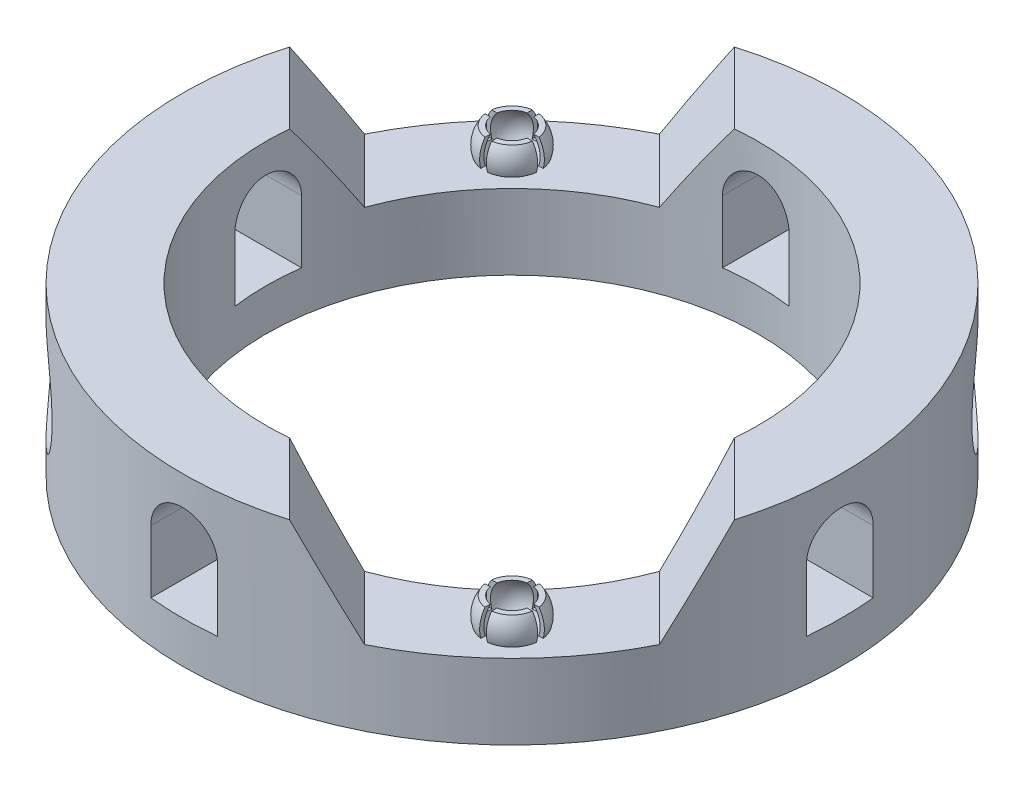
SolidWorks part; units mm, degrees
ref_plane "Front Plane" through (0, 0, 0) normal (0, 0, 1) x (1, 0, 0)
ref_plane "Top Plane" through (0, 0, 0) normal (0, 1, 0) x (1, 0, 0)
ref_plane "Right Plane" through (0, 0, 0) normal (1, 0, 0) x (0, 0, -1)
sketch "Sketch1" plane through (0, 0, 0) normal (0, 1, 0) x (1, 0, 0)
  circle A0 centre (0, 0) radius 29.5
  circle A1 centre (0, 0) radius 39.5
  dimension "D1" = 59
  dimension "D2" = 79
extrude "Boss-Extrude1" add sketch "Sketch1" along normal blind 20
ref_plane "Plane1" through (0, 0, 0) normal (0.7071, 0, -0.7071) x (-0.7071, 0, -0.7071)
sketch "Sketch2" plane through (0, 0, 0) normal (1, 0, 0) x (0, 0, -1)
  line L0 (0, 0) -> (0, 30.0667) construction
  line L1 (4, 5) -> (-4, 5)
  line L2 (-4, 5) -> (-4, 12.5)
  line L3 (4, 5) -> (4, 12.5)
  arc A0 (-4, 12.5) -> (4, 12.5) centre (0, 12.5) cw
  dimension "D6" = 4
  dimension "D1" = 8
  dimension "D2" = 4
  dimension "D3" = 5
  dimension "D4" = 7.5
  dimension "D5" = 7.5
extrude "Cut-Extrude1" cut sketch "Sketch2" against normal through all
extrude "Cut-Extrude2" cut sketch "Sketch2<2>" along normal through all
sketch "Sketch2<2>" plane through (0, 0, 0) normal (1, 0, 0) x (0, 0, -1) same geometry as "Sketch2"
mirror "Mirror1" about plane through (0, 0, 0) normal (0.7071, 0, -0.7071) of "Cut-Extrude2", "Cut-Extrude1"
sketch "Sketch4" plane through (0, 0, 0) normal (0.7071, 0, -0.7071) x (-0.7071, 0, -0.7071)
  line L0 (0, 0) -> (0, 44.1067) construction
  circle A0 centre (0, 10) radius 3.175
  dimension "D1" = 6.35
  dimension "D2" = 10
extrude "Cut-Extrude3" cut sketch "Sketch4" against normal up to next
extrude "Cut-Extrude4" cut sketch "Sketch4<2>" along normal up to next
sketch "Sketch4<2>" plane through (0, 0, 0) normal (0.7071, 0, -0.7071) x (-0.7071, 0, -0.7071) same geometry as "Sketch4"
ref_plane "Plane2" through (0, 0, 0) normal (0.7071, 0, 0.7071) x (0.7071, 0, -0.7071)
sketch "Sketch5" plane through (0, 20, 0) normal (0, 1, 0) x (1, 0, 0)
  line L0 (13.6827, -13.6827) -> (-13.6827, 13.6827) construction
  line L1 (-27.9307, 27.9307) -> (27.9307, -27.9307) construction
  line L2 (25.4558, -28.9914) -> (28.9914, -25.4558)
  line L3 (25.4558, -28.9914) -> (19.799, -23.3345)
  line L4 (28.9914, -25.4558) -> (23.3345, -19.799)
  line L5 (19.799, -23.3345) -> (23.3345, -19.799)
  line L6 (25.4558, -28.9914) -> (23.3345, -19.799) construction
  line L7 (28.9914, -25.4558) -> (19.799, -23.3345) construction
  circle A0 centre (0, 0) radius 39.5 construction
  circle A1 centre (0, 0) radius 29.5 construction
  point P7 (24.3952, -24.3952)
  dimension "D1" = 34.5
  dimension "D2" = 8
  dimension "D3" = 5
extrude "Boss-Extrude2" add sketch "Sketch5" along normal blind 13
sketch "Sketch6" plane through (1.7678, 0, -1.7678) normal (0.7071, 0, -0.7071) x (-0.7071, 0, -0.7071)
  line L0 (-38.5, 33) -> (-38.5, 20) construction
  line L1 (-38.5, 33) -> (-30.5, 33) construction
  line L2 (-30.5, 33) -> (-30.5, 20) construction
  line L4 (-38.5, 28) -> (-38.5, 33)
  line L8 (-38.5, 33) -> (-30.5, 33)
  line L9 (-30.5, 33) -> (-30.5, 28)
  arc A0 (-38.5, 28) -> (-30.5, 28) centre (-34.5, 28) cw
  dimension "D3" = 4
  dimension "D1" = 4
  dimension "D2" = 5
extrude "Cut-Extrude7" cut sketch "Sketch6" against normal up to next
sketch "Sketch7" plane through (1.7678, 0, -1.7678) normal (0.7071, 0, -0.7071) x (-0.7071, 0, -0.7071)
  circle A0 centre (-34.5, 28) radius 1
  dimension "D1" = 2
extrude "Cut-Extrude8" cut sketch "Sketch7" against normal up to next
ref_plane "Plane3" through (27.9307, 0, -27.9307) normal (0.7071, 0, -0.7071) x (-0.7071, 0, -0.7071)
sketch "Sketch8" plane through (27.9307, 0, -27.9307) normal (0.7071, 0, -0.7071) x (-0.7071, 0, -0.7071)
  circle A0 centre (0, 10) radius 6.35
  dimension "D1" = 12.7
extrude "Cut-Extrude9" cut sketch "Sketch8" against normal blind 1
mirror "Mirror3" about plane through (0, 0, 0) normal (0.7071, 0, -0.7071) of "Cut-Extrude9"
ref_plane "Plane4" through (0, 0, 0) normal (0.7071, 0, -0.7071) x (-0.7071, 0, -0.7071)
ref_plane "Plane5" through (0, 10, 0) normal (0, 1, 0) x (1, 0, 0)
ref_axis "Ball Join Axis" through (-41.2502, 10, -41.2502) along (0.7071, 0, 0.7071)
sketch "Sketch9" plane through (0, 20, 0) normal (0, 1, 0) x (1, 0, 0)
  line L3 (-17.6234, 26.1087) -> (-21.9323, 30.4175)
  line L4 (-26.1087, 17.6234) -> (-30.4175, 21.9323)
  line L5 (-41.2502, 41.2502) -> (45.8258, -45.8258) construction
  arc A0 (-17.6234, 26.1087) -> (-26.1087, 17.6234) centre (0, 0) ccw
  arc A1 (-21.9323, 30.4175) -> (-30.4175, 21.9323) centre (0, 0) ccw
  dimension "D3" = 37.5
  dimension "D4" = 31.5
  dimension "D1" = 6
  dimension "D2" = 6
extrude "Cut-Extrude11" cut sketch "Sketch9" against normal blind 15 contours A1 L4 A0 L3
sketch "Sketch10" plane through (0, 0, 0) normal (0.7071, 0, 0.7071) x (0.7071, 0, -0.7071)
  circle A0 centre (0, 10) radius 1.5
  dimension "D2" = 3
  dimension "D1" = 0
extrude "Cut-Extrude12" cut sketch "Sketch10" against normal blind 40
ref_plane "Plane8" through (0, 35, 0) normal (0, 1, 0) x (1, 0, 0)
sketch "Sketch15" plane through (0, 35, 0) normal (0, 1, 0) x (1, 0, 0)
  line L0 (-17.6564, 35.3341) -> (-10.0556, 27.7333)
  line L1 (-35.3341, 17.6564) -> (-27.7333, 10.0556)
  line L2 (10.0556, -27.7333) -> (17.6564, -35.3341)
  line L3 (27.7333, -10.0556) -> (35.3341, -17.6564)
  line L4 (-41.2502, 41.2502) -> (45.8258, -45.8258) construction
  arc A0 (17.6564, -35.3341) -> (35.3341, -17.6564) centre (0, 0) ccw
  arc A1 (-10.0556, 27.7333) -> (-27.7333, 10.0556) centre (0, 0) ccw
  arc A2 (-17.6564, 35.3341) -> (-35.3341, 17.6564) centre (0, 0) ccw
  arc A3 (10.0556, -27.7333) -> (27.7333, -10.0556) centre (0, 0) ccw
  dimension "D2" = 79
  dimension "D3" = 12.5
  dimension "D5" = 29.5
  dimension "D1" = 12.5
  dimension "D4" = 0
  dimension "0" = 0
extrude "Boss-Extrude3" add sketch "Sketch15" against normal through all contours A3 L2 A0 L3 | A1 L1 A2 L0 region at (23.8265, 35, 23.8265)
ref_plane "Plane9" through (0, 9, 0) normal (0, -1, 0) x (-1, 0, 0)
extrude "Cut-Extrude14" cut sketch "Sketch15<5>" against normal up to surface (26 mm away) contours A3 L2 A0 L3 | A2 L1 A1 L0 region at (23.8265, 35, 23.8265) up to plane "Plane9"
sketch "Sketch15<5>" plane through (0, 35, 0) normal (0, 1, 0) x (1, 0, 0) same geometry as "Sketch15"
ref_plane "Plane10" through (0, 10, 0) normal (0, 1, 0) x (1, 0, 0)
sketch "Sketch17" plane through (0, 10, 0) normal (0, 1, 0) x (1, 0, 0)
  line L5 (-41.2502, 41.2502) -> (45.8258, -45.8258) construction
  point P0 (-24.3952, 24.3952)
  point P1 (24.3952, -24.3952)
  dimension "D1" = 34.5
  dimension "D2" = 0
  dimension "D3" = 0
  dimension "D4" = 34.5
sketch "Sketch18" plane through (0, 10, 0) normal (0, 1, 0) x (1, 0, 0)
  line L0 (-24.3952, 27.8952) -> (-24.3952, 20.8952)
  line L1 (24.3952, -20.8952) -> (24.3952, -27.8952)
  arc A0 (-24.3952, 20.8952) -> (-24.3952, 27.8952) centre (-24.3952, 24.3952) ccw
  arc A1 (24.3952, -27.8952) -> (24.3952, -20.8952) centre (24.3952, -24.3952) ccw
revolve "Cut-Revolve1" cut sketch "Sketch18" angle 360 about L0 region at (-22.9097, 10, -24.3952)
revolve "Cut-Revolve2" cut sketch "Sketch18<3>" angle 360 about L1 region at (25.8806, 10, 24.3952)
sketch "Sketch18<3>" plane through (0, 10, 0) normal (0, 1, 0) x (1, 0, 0) same geometry as "Sketch18"
chamfer "Chamfer2" distance 11 angle 30 2 edges at (-31.5337, 20, -13.856) (13.856, 20, 31.5337) first distance on face at (-31.5337, 14.5, -13.856) first distance on face at (13.856, 14.5, 31.5337)
chamfer "Chamfer3" distance 11 angle 30 2 edges at (31.5337, 20, 13.856) (-13.856, 20, -31.5337) first distance on face at (31.5337, 14.5, 13.856) first distance on face at (-13.856, 14.5, -31.5337)
sketch "Sketch21" plane through (0, 0, 0) normal (0.7071, 0, -0.7071) x (-0.7071, 0, -0.7071)
  line L0 (-34.5, 13.5) -> (-34.5, 13)
  line L1 (-34.5, 7) -> (-34.5, 6.5)
  arc A0 (-34.5, 6.5) -> (-34.5, 13.5) centre (-34.5, 10) ccw
  arc A1 (-34.5, 7) -> (-34.5, 13) centre (-34.5, 10) ccw
  dimension "D1" = 3.5
revolve "Revolve1" add sketch "Sketch21" angle 360 about L0
ref_plane "Plane11" through (0, 12, 0) normal (0, 1, 0) x (1, 0, 0)
sketch "Sketch24" plane through (0, 12, 0) normal (0, 1, 0) x (1, 0, 0)
  circle A0 centre (24.3952, -24.3952) radius 3.5
  dimension "D1" = 0
extrude "Cut-Extrude15" cut sketch "Sketch24" along normal through all
sketch "Sketch26" plane through (0, 12, 0) normal (0, 1, 0) x (1, 0, 0)
  line L0 (23.9952, -24.7952) -> (23.9952, -27.8952)
  line L1 (20.9181, -23.9952) -> (23.9952, -23.9952)
  line L3 (20.9181, -24.7952) -> (23.9952, -24.7952)
  line L6 (23.9952, -20.9181) -> (23.9952, -23.9952)
  line L7 (23.9952, -27.8952) -> (24.7952, -27.8952)
  line L8 (24.7952, -20.9181) -> (24.7952, -23.9952)
  line L9 (24.7952, -23.9952) -> (27.8723, -23.9952)
  line L10 (24.7952, -24.7952) -> (24.7952, -27.8952)
  line L11 (24.7952, -24.7952) -> (27.8723, -24.7952)
  arc A2 (24.7952, -20.9181) -> (23.9952, -20.9181) centre (24.3952, -24.3952) ccw
  arc A3 (20.9181, -23.9952) -> (20.9181, -24.7952) centre (24.3952, -24.3952) ccw
  arc A4 (27.8723, -24.7952) -> (27.8723, -23.9952) centre (24.3952, -24.3952) ccw
  arc A5 (23.9952, -27.8952) -> (24.7952, -27.8952) centre (24.3952, -24.3952) ccw
  point P4 (24.3952, -27.8952)
  point P5 (27.8952, -24.3952)
  point P12 (20.8952, -24.3952)
  point P14 (24.3952, -20.8952)
  circle M10 centre (24.3952, -24.3952) radius 2.2361
  circle M11 centre (24.3952, -24.3952) radius 2.8723
  dimension "D1" = 7
  dimension "D6" = 0.4
  dimension "D2" = 7
  dimension "D3" = 3.5
  dimension "D4" = 0.8
  dimension "D5" = 0.4
  dimension "D7" = 0.8
  dimension "D8" = 3.5
extrude "Cut-Extrude18" cut sketch "Sketch26" against normal up to surface (3 mm away) contours L1 A3 L3 M11 | L3 L1 M11 M10 | L10 L11 L9 L8 L6 L1 L3 L0 M10 | L8 L6 M11 M10 | L8 A2 L6 M11 | L11 L9 M10 M11 | L11 A4 L9 M11 | L10 L0 L7 M11 | L10 L0 M10 M11 region at (24.3952, 12, 24.3952) region at (24.3952, 12, 26.9387) region at (21.8517, 12, 24.3952) region at (24.3952, 12, 27.5766) region at (21.2175, 12, 24.3952) region at (26.9387, 12, 24.3952) region at (24.3952, 12, 21.8517) region at (27.5728, 12, 24.3952) region at (24.3952, 12, 21.2175) up to face at (24.3952, 9, 21.0411)
ref_plane "Plane12" through (0, 0, 0) normal (0.7071, 0, 0.7071) x (0.7071, 0, -0.7071)
mirror "Mirror5" about plane through (0, 0, 0) normal (0.7071, 0, 0.7071) of "Cut-Extrude18", "Revolve1", "Cut-Extrude15"
